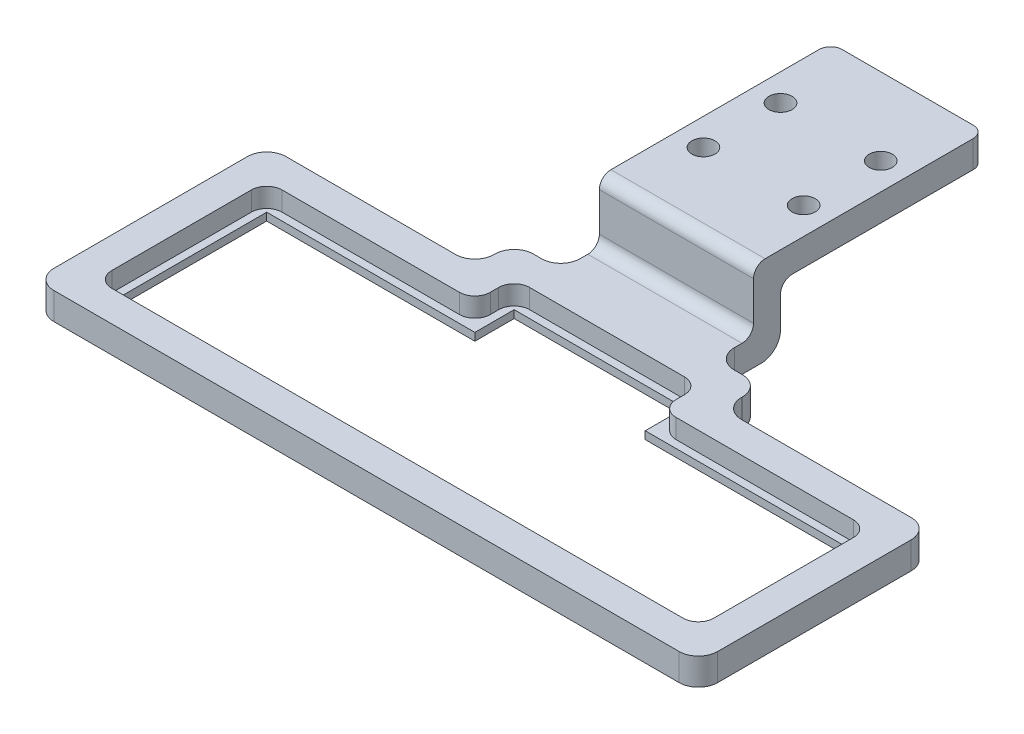
SolidWorks part; units mm, degrees
ref_plane "Plano frontal" through (0, 0, 0) normal (0, 0, 1) x (1, 0, 0)
ref_plane "Plano superior" through (0, 0, 0) normal (0, 1, 0) x (1, 0, 0)
ref_plane "Plano direito" through (0, 0, 0) normal (1, 0, 0) x (0, 0, -1)
sketch "Esboço1" plane through (0, 0, 0) normal (0, 1, 0) x (1, 0, 0)
  line L0 (12.05, 11.05) -> (39.05, 11.05)
  line L1 (-39.05, -11.05) -> (39.05, -11.05)
  line L2 (-39.05, -11.05) -> (-39.05, 11.05)
  line L3 (-39.05, 11.05) -> (-12.05, 11.05)
  line L4 (39.05, -11.05) -> (39.05, 11.05)
  line L5 (-39.05, -11.05) -> (39.05, 11.05) construction
  line L6 (-39.05, 11.05) -> (39.05, -11.05) construction
  line L7 (-12.05, 16.15) -> (12.05, 16.15)
  line L8 (-12.05, 16.15) -> (-12.05, 11.05)
  line L10 (12.05, 16.15) -> (12.05, 11.05)
  line L11 (-12.05, 16.15) -> (12.05, 11.05) construction
  line L12 (-12.05, 11.05) -> (12.05, 16.15) construction
  line L13 (-16.05, 20.15) -> (16.05, 20.15)
  line L14 (16.05, 20.15) -> (16.05, 15.05)
  line L15 (16.05, 15.05) -> (43.05, 15.05)
  line L16 (43.05, -15.05) -> (43.05, 15.05)
  line L17 (-43.05, -15.05) -> (43.05, -15.05)
  line L18 (-43.05, -15.05) -> (-43.05, 15.05)
  line L19 (-43.05, 15.05) -> (-16.05, 15.05)
  line L20 (-16.05, 20.15) -> (-16.05, 15.05)
  point P0 (0, 0)
  point P5 (0, 13.6)
  point P11 (0, 0)
  dimension "D1" = 78.1
  dimension "D2" = 22.1
  dimension "D3" = 5.1
  dimension "D4" = 24.1
  dimension "D5" = 4
extrude "Ressalto-extrusão1" add sketch "Esboço1" along normal blind 3.5
sketch "Esboço2" plane through (0, 0, 0) normal (0, -1, 0) x (1, 0, 0)
  line L8 (39.05, 11.05) -> (39.05, -11.05) construction
  line L9 (39.05, -11.05) -> (12.05, -11.05) construction
  line L10 (12.05, -11.05) -> (12.05, -16.15) construction
  line L11 (12.05, -16.15) -> (-12.05, -16.15) construction
  line L12 (-12.05, -16.15) -> (-12.05, -11.05) construction
  line L13 (-12.05, -11.05) -> (-39.05, -11.05) construction
  line L14 (-39.05, -11.05) -> (-39.05, 11.05) construction
  line L15 (-39.05, 11.05) -> (39.05, 11.05) construction
  line L32 (38.05, -10.05) -> (38.05, 10.05)
  line L33 (11.05, -10.05) -> (38.05, -10.05)
  line L34 (11.05, -15.15) -> (11.05, -10.05)
  line L35 (-11.05, -10.05) -> (-11.05, -15.15)
  line L36 (-11.05, -15.15) -> (11.05, -15.15)
  line L37 (-38.05, -10.05) -> (-11.05, -10.05)
  line L38 (-38.05, 10.05) -> (-38.05, -10.05)
  line L39 (38.05, 10.05) -> (-38.05, 10.05)
  line L40 (38.05, -10.05) -> (38.05, 10.05)
  line L41 (11.05, -10.05) -> (38.05, -10.05)
  line L42 (11.05, -15.15) -> (11.05, -10.05)
  line L43 (-11.05, -10.05) -> (-11.05, -15.15)
  line L44 (-11.05, -15.15) -> (11.05, -15.15)
  line L45 (-38.05, -10.05) -> (-11.05, -10.05)
  line L46 (-38.05, 10.05) -> (-38.05, -10.05)
  line L47 (38.05, 10.05) -> (-38.05, 10.05)
  line L48 (39.05, 11.05) -> (39.05, -11.05)
  line L49 (39.05, -11.05) -> (12.05, -11.05)
  line L50 (12.05, -11.05) -> (12.05, -16.15)
  line L51 (12.05, -16.15) -> (-12.05, -16.15)
  line L52 (-12.05, -16.15) -> (-12.05, -11.05)
  line L53 (-12.05, -11.05) -> (-39.05, -11.05)
  line L54 (-39.05, -11.05) -> (-39.05, 11.05)
  line L55 (-39.05, 11.05) -> (39.05, 11.05)
  dimension "D2" = 1
extrude "Ressalto-extrusão2" add sketch "Esboço2" against normal blind 1
sketch "Esboço3" plane through (0, 0, 0) normal (1, 0, 0) x (0, 0, -1)
  line L0 (20.15, 0) -> (28.65, 0)
  line L1 (28.65, 0) -> (28.65, 8) construction
  line L2 (28.65, 8) -> (55.15, 8) construction
  line L3 (55.15, 8) -> (55.15, 11.5)
  line L4 (55.15, 11.5) -> (25.15, 11.5)
  line L5 (25.15, 11.5) -> (25.15, 3.5)
  line L6 (25.15, 3.5) -> (20.15, 3.5)
  line L7 (20.15, 3.5) -> (20.15, 0) construction
  line L8 (25.15, 3.5) -> (28.65, 3.5) construction
  line L9 (20.15, 3.5) -> (20.15, 0)
  line L10 (28.65, 3.5) -> (43.5563, 8)
  line L11 (28.65, 0) -> (55.15, 8)
  line L12 (28.65, 3.5) -> (28.65, 8)
  line L13 (28.65, 8) -> (43.5563, 8)
  dimension "D1" = 8
  dimension "D2" = 5
  dimension "D3" = 35
extrude "Ressalto-extrusão3" add sketch "Esboço3" against normal blind 10 and the other way blind 10
sketch "Esboço4" plane through (10, 0, 0) normal (1, 0, 0) x (0, 0, -1)
  line L0 (20.15, 0) -> (28.65, 0) construction
  line L1 (55.15, 8) -> (28.65, 8)
  line L2 (55.15, 8) -> (55.15, 0)
  line L3 (55.15, 0) -> (28.65, 0)
  line L4 (28.65, 8) -> (28.65, 0)
  line L5 (28.65, 0) -> (55.15, 8) construction
extrude "Corte-extrusão1" cut sketch "Esboço4" against normal blind 7
extrude "Corte-extrusão2" cut sketch "Esboço4<2>" along normal blind 7 from surface starting at face at (-10, 6.5, -33.6187)
sketch "Esboço4<2>" plane through (10, 0, 0) normal (1, 0, 0) x (0, 0, -1) same geometry as "Esboço4"
sketch "Esboço5" plane through (0, 8, 0) normal (0, -1, 0) x (1, 0, 0)
  line L0 (10, -55.15) -> (3, -55.15) construction
  line L1 (-3, -55.15) -> (-10, -55.15) construction
  circle A0 centre (-6.5, -45.15) radius 1.5
  circle A1 centre (6.5, -45.15) radius 1.5
  circle A2 centre (-6.5, -35.15) radius 1.5
  circle A3 centre (6.5, -35.15) radius 1.5
  point P10 (0, 0)
  point P11 (0, 0)
  point P12 (0, 0)
  point P13 (6.5, -55.15)
  point P14 (0, 0)
  point P17 (-6.5, -55.15)
  point P18 (0, 0)
  point P19 (0, 0)
  dimension "D1" = 10
  dimension "D3" = 3
  dimension "D2" = 10
extrude "Corte-extrusão3" cut sketch "Esboço5" against normal through all both and the other way through all
fillet "Filete1" radius 2 8 edges at (-12.05, 2.25, -16.15) (12.05, 2.25, -16.15) (39.05, 2.25, 11.05) (39.05, 2.25, -11.05) (12.05, 2.25, -11.05) (-39.05, 2.25, 11.05) (-39.05, 2.25, -11.05) (-12.05, 2.25, -11.05)
fillet "Filete2" radius 2.5 10 edges at (-10, 1.75, -20.15) (10, 1.75, -20.15) (16.05, 1.75, -20.15) (16.05, 1.75, -15.05) (43.05, 1.75, -15.05) (43.05, 1.75, 15.05) (-43.05, 1.75, 15.05) (-43.05, 1.75, -15.05) (-16.05, 1.75, -20.15) (-16.05, 1.75, -15.05)
fillet "Filete3" radius 1.5 7 edges at (-10, 9.75, -55.15) (10, 9.75, -55.15) (0, 11.5, -25.15) (0, 3.5, -25.15) (0, 8, -28.65) (0, 8, -43.5562) (0, 3.5, -28.65)
sketch "Esboço6" plane through (10, 0, 0) normal (1, 0, 0) x (0, 0, -1)
  line L0 (28.65, 6.5) -> (28.65, 0) construction
  line L1 (22.65, 0) -> (28.65, 0) construction
  line L2 (26.15, 0) -> (26.15, 2.5) construction
  line L3 (26.15, 2.5) -> (28.65, 2.5) construction
  line L4 (26.15, 0) -> (28.65, 0)
  line L5 (28.65, 2.5) -> (28.65, 0)
  arc A0 (28.65, 2.5) -> (26.15, 0) centre (26.15, 2.5) cw
  dimension "D1" = 2.5
extrude "Corte-extrusão4" cut sketch "Esboço6" against normal up to surface (7 mm away) up to face at (3, 5.0614, -35.1946)
extrude "Corte-extrusão5" cut sketch "Esboço6<2>" along normal up to surface (-13 mm away) from surface up to face at (-3, 5.0614, -35.1946) starting at face at (-10, 6.1646, -30.9399)
sketch "Esboço6<2>" plane through (10, 0, 0) normal (1, 0, 0) x (0, 0, -1) same geometry as "Esboço6"
